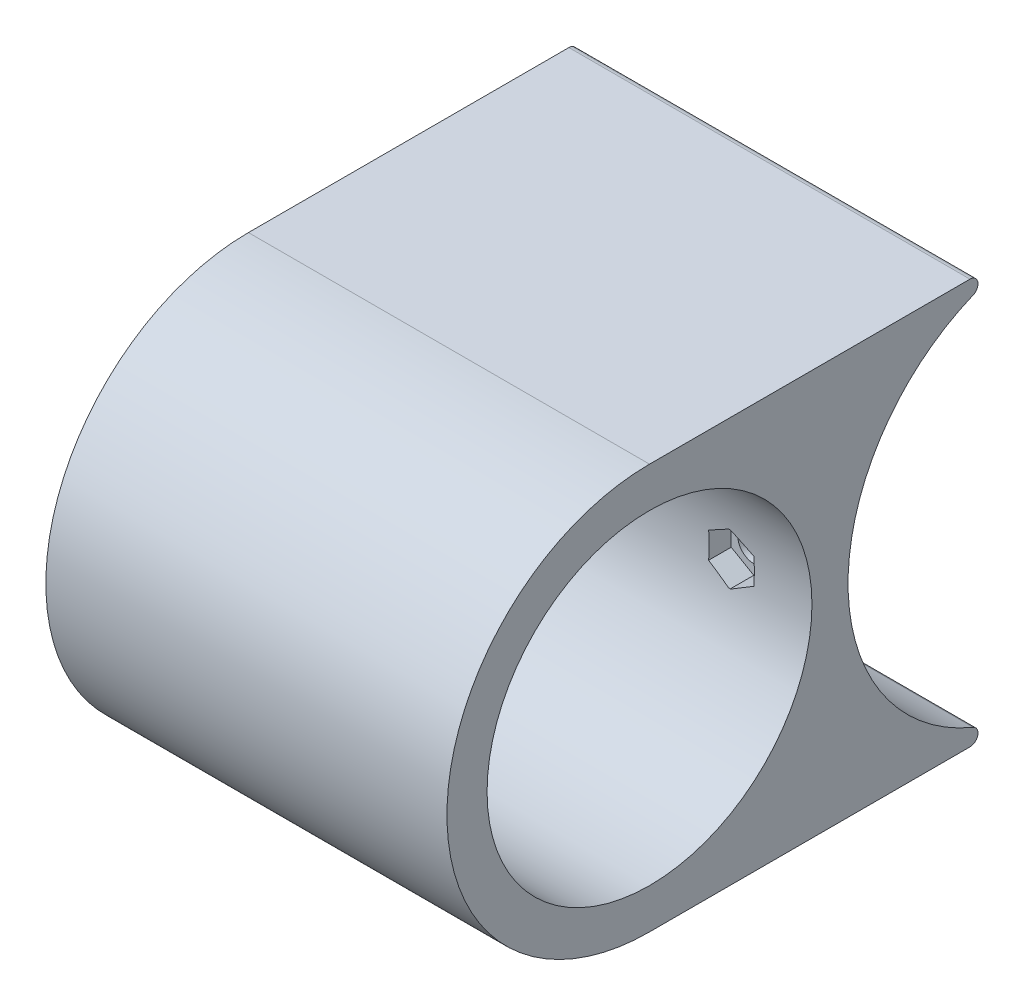
SolidWorks part; units mm, degrees
ref_plane "前视基准面" through (0, 0, 0) normal (0, 0, 1) x (1, 0, 0)
ref_plane "上视基准面" through (0, 0, 0) normal (0, 1, 0) x (1, 0, 0)
ref_plane "右视基准面" through (0, 0, 0) normal (1, 0, 0) x (0, 0, -1)
other "Configuration Table"
sketch "草图1" plane through (0, 0, 0) normal (1, 0, 0) x (0, 0, -1)
  line L0 (0, 0) -> (50, 0) construction
  line L1 (39.9501, 25.25) -> (0, 25.25)
  line L2 (39.9501, -25.25) -> (0, -25.25)
  line L3 (0, 25.25) -> (0, 0) construction
  line L4 (0, 0) -> (0, -25.25) construction
  circle A0 centre (0, 0) radius 20.25
  arc A1 (0, 25.25) -> (0, -25.25) centre (0, 0) ccw
  arc A2 (40.333, 23.3262) -> (40.333, -23.3262) centre (50, 0) ccw
  arc A3 (39.9501, -25.25) -> (40.333, -23.3262) centre (39.9501, -24.25) ccw
  arc A4 (39.9501, 25.25) -> (40.333, 23.3262) centre (39.9501, 24.25) cw
  dimension "D1" = 40.5
  dimension "D2" = 5
  dimension "D3" = 25.25
  dimension "D5" = 1
  dimension "D4" = 50
extrude "凸台-拉伸1" add sketch "草图1" along normal blind 25 and the other way blind 25
sketch "草图2" plane through (0, 0, 0) normal (0, 0, 1) x (1, 0, 0)
  line L0 (-1000, 0) -> (49000, 0) construction
  line L1 (-25, 25.25) -> (-25, -25.25) construction
  line L2 (25, -25.25) -> (25, 25.25) construction
  circle A1 centre (-15, 0) radius 2
  circle A2 centre (15, 0) radius 2
  dimension "D1" = 4
  dimension "D2" = 4
  dimension "D3" = 10
  dimension "D4" = 10
extrude "切除-拉伸1" cut sketch "草图2" against normal blind 41
ref_plane "基准面1" through (0, 0, -20) normal (0, 0, 1) x (1, 0, 0)
sketch "草图3" plane through (0, 0, -20) normal (0, 0, 1) x (1, 0, 0)
  line L0 (-15, 3.25) -> (-17.8146, 1.625)
  line L1 (-17.8146, 1.625) -> (-17.8146, -1.625)
  line L2 (-17.8146, -1.625) -> (-15, -3.25)
  line L3 (-15, -3.25) -> (-12.1854, -1.625)
  line L4 (-12.1854, -1.625) -> (-12.1854, 1.625)
  line L5 (-12.1854, 1.625) -> (-15, 3.25)
  line L6 (15, 3.25) -> (12.1854, 1.625)
  line L7 (12.1854, 1.625) -> (12.1854, -1.625)
  line L8 (12.1854, -1.625) -> (15, -3.25)
  line L9 (15, -3.25) -> (17.8146, -1.625)
  line L10 (17.8146, -1.625) -> (17.8146, 1.625)
  line L11 (17.8146, 1.625) -> (15, 3.25)
  circle A0 centre (-15, 0) radius 3.25 construction
  circle A1 centre (15, 0) radius 3.25 construction
  dimension "D1" = 6.5
  dimension "D2" = 6.5
  dimension "D3" = 120
  dimension "D4" = 120
extrude "切除-拉伸2" cut sketch "草图3" against normal blind 3
